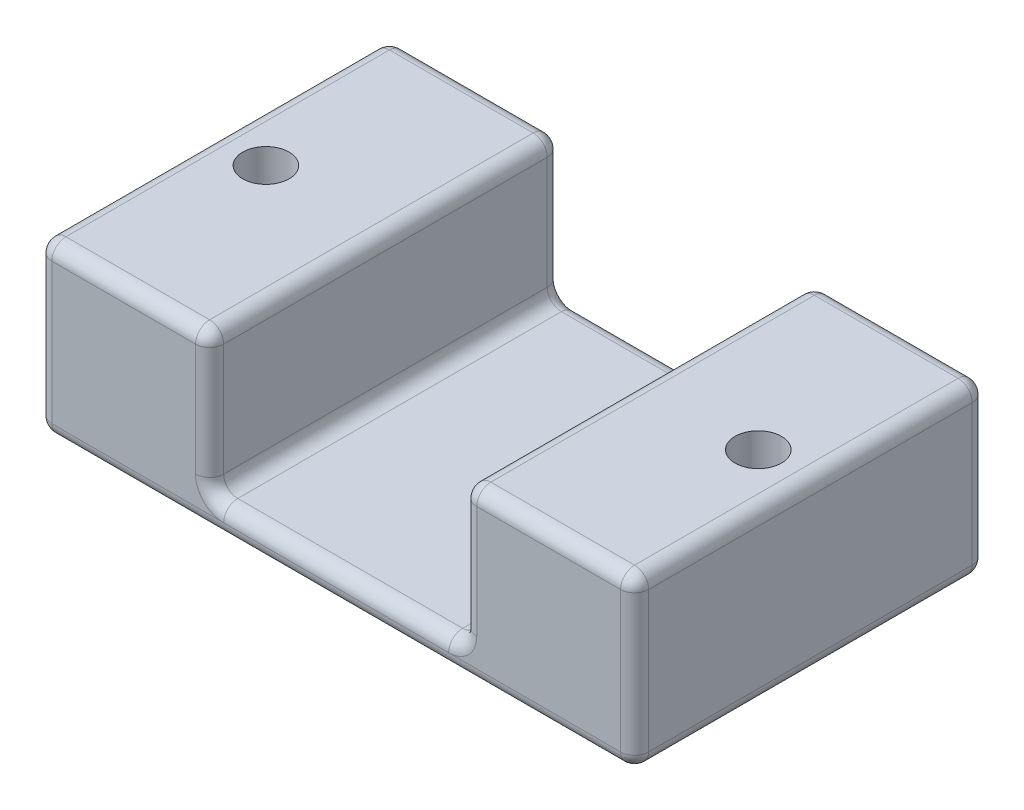
SolidWorks part; units mm, degrees
ref_plane "正面" through (0, 0, 0) normal (0, 0, 1) x (1, 0, 0)
ref_plane "平面" through (0, 0, 0) normal (0, 1, 0) x (1, 0, 0)
ref_plane "右側面" through (0, 0, 0) normal (1, 0, 0) x (0, 0, -1)
sketch "ｽｹｯﾁ1" plane through (0, 0, 0) normal (0, 1, 0) x (1, 0, 0)
  line L1 (-21.215, -12.5) -> (21.215, -12.5)
  line L2 (-21.215, -12.5) -> (-21.215, 12.5)
  line L3 (-21.215, 12.5) -> (21.215, 12.5)
  line L4 (21.215, -12.5) -> (21.215, 12.5)
  line L5 (-21.215, -12.5) -> (21.215, 12.5) construction
  line L6 (-21.215, 12.5) -> (21.215, -12.5) construction
  point P0 (0, 0)
  dimension "D1" = 25
  dimension "D2" = 42.43
extrude "ﾎﾞｽ - 押し出し1" add sketch "ｽｹｯﾁ1" along normal blind 2
sketch "ｽｹｯﾁ2" plane through (0, 2, 0) normal (0, 1, 0) x (1, 0, 0)
  line L0 (21.215, 12.5) -> (-21.215, 12.5) construction
  line L1 (-21.215, -12.5) -> (-8.995, -12.5)
  line L2 (-21.215, -12.5) -> (-21.215, 12.5)
  line L3 (-21.215, 12.5) -> (-8.995, 12.5)
  line L4 (-8.995, -12.5) -> (-8.995, 12.5)
  line L6 (21.215, -12.5) -> (8.995, -12.5)
  line L7 (21.215, -12.5) -> (21.215, 12.5)
  line L8 (21.215, 12.5) -> (8.995, 12.5)
  line L9 (8.995, -12.5) -> (8.995, 12.5)
  dimension "D2" = 12.22
extrude "ﾎﾞｽ - 押し出し2" add sketch "ｽｹｯﾁ2" along normal blind 10
sketch "ｽｹｯﾁ3" plane through (0, 12, 0) normal (0, 1, 0) x (1, 0, 0)
  line L0 (-8.995, 12.5) -> (-21.215, 12.5) construction
  line L1 (21.215, 12.5) -> (8.995, 12.5) construction
  line L5 (-21.215, 12.5) -> (-21.215, -12.5) construction
  circle A0 centre (-17.495, 0) radius 1.65
  circle A1 centre (17.505, 0) radius 1.65
  dimension "D1" = 3.3
  dimension "D2" = 3.3
  dimension "D3" = 12.5
  dimension "D4" = 12.5
  dimension "D5" = 3.72
  dimension "D6" = 35
extrude "ｶｯﾄ - 押し出し1" cut sketch "ｽｹｯﾁ3" against normal through all
sketch "ｽｹｯﾁ4" plane through (0, 0, 0) normal (0, 0, 1) x (1, 0, 0)
  line L0 (-11.995, 0) -> (-8.995, -3)
  line L1 (-8.995, -3) -> (8.995, -3)
  line L2 (8.995, -3) -> (11.995, 0)
  line L8 (-21.215, 0) -> (21.215, 0)
  line L9 (21.215, 0) -> (21.215, 12)
  line L10 (21.215, 12) -> (8.995, 12)
  line L11 (8.995, 12) -> (8.995, 2)
  line L12 (8.995, 2) -> (-8.995, 2)
  line L13 (-8.995, 2) -> (-8.995, 12)
  line L14 (-8.995, 12) -> (-21.215, 12)
  line L15 (-21.215, 12) -> (-21.215, 0)
  line L16 (-11.995, 0) -> (11.995, 0)
  line L17 (21.215, 0) -> (21.215, 12)
  line L18 (21.215, 12) -> (8.995, 12)
  line L19 (8.995, 12) -> (8.995, 2)
  line L20 (8.995, 2) -> (-8.995, 2)
  line L21 (-8.995, 2) -> (-8.995, 12)
  line L22 (-8.995, 12) -> (-21.215, 12)
  line L23 (-21.215, 12) -> (-21.215, 0)
  dimension "D2" = 3
  dimension "D3" = 3
  dimension "D1" = 0
extrude "ﾎﾞｽ - 押し出し3" add sketch "ｽｹｯﾁ4" along normal blind 3 and the other way blind 3 contours L1 L2 L16 L0
fillet "ﾌｨﾚｯﾄ2" radius 1 32 edges at (-8.995, 7, 12.5) (-8.995, 7, -12.5) (8.995, 7, 12.5) (8.995, 7, -12.5) (11.995, 0, 0) (8.995, -3, 0) (0, -3, 3) (0, 0, 3) (-8.995, -3, 0) (-11.995, 0, 0) (0, 0, -3) (0, -3, -3) (0, 0, 12.5) (0, 0, -12.5) (-21.215, 0, 0) (21.215, 0, 0) (21.215, 6, -12.5) (21.215, 6, 12.5) (-21.215, 6, -12.5) (-21.215, 6, 12.5) (21.215, 12, 0) (-21.215, 12, 0) (-15.105, 12, 12.5) (-15.105, 12, -12.5) (15.105, 12, -12.5) (15.105, 12, 12.5) (8.995, 12, 0) (-8.995, 12, 0) (-8.995, 2, 0) (0, 2, 12.5) (0, 2, -12.5) (8.995, 2, 0)
sketch "ｽｹｯﾁ5" plane through (0, 0, 0) normal (0, -1, 0) x (-1, 0, 0)
  circle A0 centre (-17.505, 0) radius 3.25
  circle A1 centre (17.495, 0) radius 3.25
  dimension "D1" = 6.5
extrude "ｶｯﾄ - 押し出し2" cut sketch "ｽｹｯﾁ5" against normal blind 3
